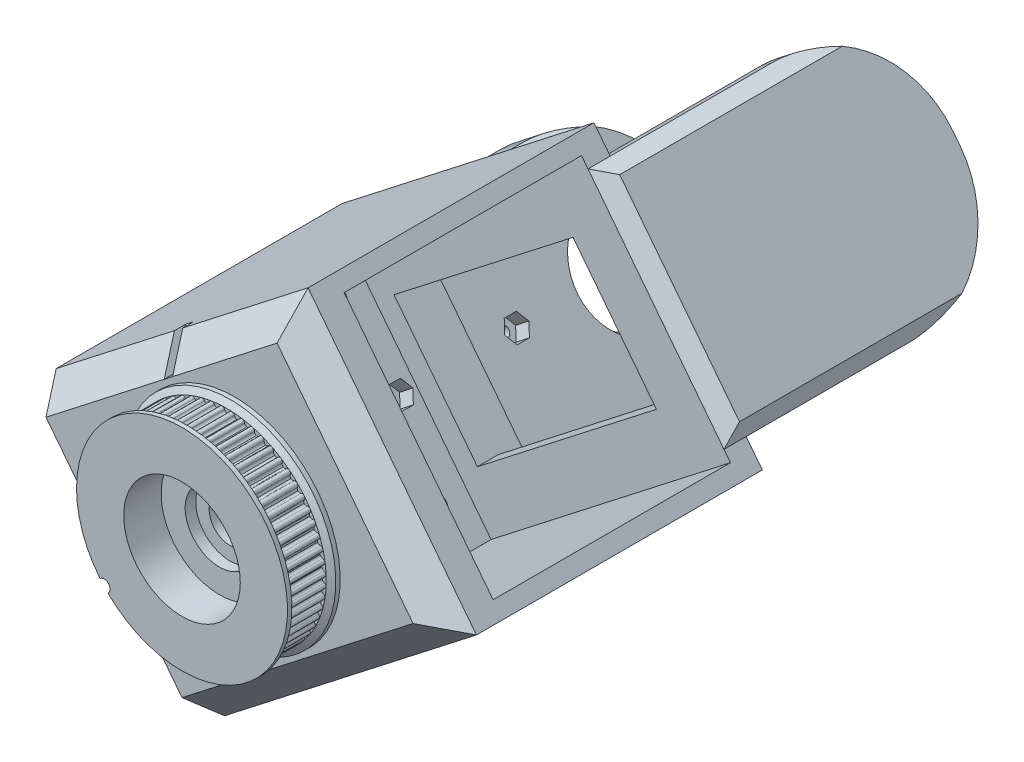
SolidWorks part; units mm, degrees
note: '?' marks a value the reader was unsure of.
other "Camera1"
other "Camera2"
other "Camera3"
ref_plane "Front" through (0, 0, 0) normal (0, 0, 1) x (1, 0, 0)
ref_plane "Top" through (0, 0, 0) normal (0, 1, 0) x (1, 0, 0)
ref_plane "Right" through (0, 0, 0) normal (1, 0, 0) x (0, 0, -1)
sketch "Sketch1" plane through (0, 0, 0) normal (1, 0, 0) x (0, 0, -1)
  line L0 (0, 0) -> (-24.4032, 0) construction
  line L3 (0, 7.1) -> (0, 18.3141)
  line L4 (-1.5, 18.85) -> (-8.5, 18.85)
  line L5 (-10, 20) -> (-10, 7.1)
  line L6 (-10, 7.1) -> (0, 7.1)
  line L7 (0, 18.3141) -> (0, 20)
  line L9 (-0.836, 20) -> (-1.5, 18.85)
  line L10 (-10, 13.3586) -> (0, 13.3586) construction
  line L11 (-5, 18.85) -> (-5, 22.0506) construction
  line L12 (-9.164, 20) -> (-8.5, 18.85)
  line L15 (-10, 20) -> (-8.5, 18.85) construction
  line L16 (-1.5, 18.85) -> (0, 18.3141) construction
  line L17 (-10, 20) -> (-9.164, 20)
  line L18 (-0.836, 20) -> (0, 20)
  point P24 (-5, 13.3586)
  dimension "D2" = 10
  dimension "D3" = 7
  dimension "D4" = 37.7
  dimension "D5" = 40
  dimension "D6" = 120
  dimension "D8" = 14.2
revolve "Revolve1" add sketch "Sketch1" angle 360 about L0
ref_plane "Plane2" through (0, 0, 1.5) normal (0, 0, 1) x (1, 0, 0)
ref_plane "Plane3" through (0, 0, 8.5) normal (0, 0, 1) x (1, 0, 0)
sketch "Sketch3" plane through (0, 0, 1.5) normal (0, 0, 1) x (1, 0, 0)
  line L0 (0.4895, 18.4804) -> (0.4858, 18.4697)
  line L1 (-0.4323, 18.471) -> (-0.436, 18.4817)
  line L2 (-1.3914, 18.4344) -> (-1.394, 18.4234)
  line L3 (-2.3607, 18.3247) -> (-2.3654, 18.3349)
  line L4 (-3.3107, 18.188) -> (-3.3122, 18.1768)
  line L5 (-4.2632, 17.9775) -> (-4.269, 17.9872)
  line L6 (-5.1937, 17.7423) -> (-5.194, 17.731)
  line L7 (-6.119, 17.4334) -> (-6.1258, 17.4424)
  line L8 (-7.0199, 17.1022) -> (-7.019, 17.0909)
  line L9 (-7.9078, 16.6983) -> (-7.9155, 16.7066)
  line L10 (-8.7691, 16.2747) -> (-8.767, 16.2636)
  line L11 (-9.6099, 15.7803) -> (-9.6184, 15.7877)
  line L12 (-10.4222, 15.269) -> (-10.419, 15.2581)
  line L13 (-11.2067, 14.6893) -> (-11.216, 14.6958)
  line L14 (-11.9612, 14.0959) -> (-11.9568, 14.0855)
  line L15 (-12.6808, 13.4374) -> (-12.6907, 13.4429)
  line L16 (-13.3691, 12.7684) -> (-13.3637, 12.7585)
  line L17 (-14.0159, 12.0383) -> (-14.0263, 12.0427)
  line L18 (-14.6305, 11.301) -> (-14.6241, 11.2917)
  line L19 (-15.1975, 10.5073) -> (-15.2083, 10.5106)
  line L20 (-15.7316, 9.7098) -> (-15.7243, 9.7012)
  line L21 (-16.2125, 8.8612) -> (-16.2236, 8.8633)
  line L22 (-16.6604, 8.0122) -> (-16.6522, 8.0044)
  line L23 (-17.05, 7.118) -> (-17.0612, 7.1189)
  line L24 (-17.4066, 6.2268) -> (-17.3977, 6.22)
  line L25 (-17.7006, 5.2968) -> (-17.7119, 5.2965)
  line L26 (-17.9621, 4.3732) -> (-17.9525, 4.3673)
  line L27 (-18.1573, 3.4175) -> (-18.1685, 3.4161)
  line L28 (-18.3209, 2.4717) -> (-18.3107, 2.4669)
  line L29 (-18.415, 1.5008) -> (-18.426, 1.4983)
  line L30 (-18.4789, 0.5431) -> (-18.4682, 0.5394)
  line L31 (-18.471, -0.4323) -> (-18.4817, -0.436)
  line L32 (-18.4344, -1.3914) -> (-18.4234, -1.394)
  line L33 (-18.3247, -2.3607) -> (-18.3349, -2.3654)
  line L34 (-18.188, -3.3107) -> (-18.1768, -3.3122)
  line L35 (-17.9775, -4.2632) -> (-17.9872, -4.269)
  line L36 (-17.7423, -5.1937) -> (-17.731, -5.194)
  line L37 (-17.4334, -6.119) -> (-17.4424, -6.1258)
  line L38 (-17.1022, -7.0199) -> (-17.0909, -7.019)
  line L39 (-16.6983, -7.9078) -> (-16.7066, -7.9155)
  line L40 (-16.2747, -8.7691) -> (-16.2636, -8.767)
  line L41 (-15.7803, -9.6099) -> (-15.7877, -9.6184)
  line L42 (-15.269, -10.4222) -> (-15.2581, -10.419)
  line L43 (-14.6893, -11.2067) -> (-14.6958, -11.216)
  line L44 (-14.0959, -11.9612) -> (-14.0855, -11.9568)
  line L45 (-13.4374, -12.6808) -> (-13.4429, -12.6907)
  line L46 (-12.7684, -13.3691) -> (-12.7585, -13.3637)
  line L47 (-12.0383, -14.0159) -> (-12.0427, -14.0263)
  line L48 (-11.301, -14.6305) -> (-11.2917, -14.6241)
  line L49 (-10.5073, -15.1975) -> (-10.5106, -15.2083)
  line L50 (-9.7098, -15.7316) -> (-9.7012, -15.7243)
  line L51 (-8.8612, -16.2125) -> (-8.8633, -16.2236)
  line L52 (-8.0122, -16.6604) -> (-8.0044, -16.6522)
  line L53 (-7.118, -17.05) -> (-7.1189, -17.0612)
  line L54 (-6.2268, -17.4066) -> (-6.22, -17.3977)
  line L55 (-5.2968, -17.7006) -> (-5.2965, -17.7119)
  line L56 (-4.3732, -17.9621) -> (-4.3673, -17.9525)
  line L57 (-3.4175, -18.1573) -> (-3.4161, -18.1685)
  line L58 (-2.4717, -18.3209) -> (-2.4669, -18.3107)
  line L59 (-1.5008, -18.415) -> (-1.4983, -18.426)
  line L60 (-0.5431, -18.4789) -> (-0.5394, -18.4682)
  line L61 (0.4323, -18.471) -> (0.436, -18.4817)
  line L62 (1.3914, -18.4344) -> (1.394, -18.4234)
  line L63 (2.3607, -18.3247) -> (2.3654, -18.3349)
  line L64 (3.3107, -18.188) -> (3.3122, -18.1768)
  line L65 (4.2632, -17.9775) -> (4.269, -17.9872)
  line L66 (5.1937, -17.7423) -> (5.194, -17.731)
  line L67 (6.119, -17.4334) -> (6.1258, -17.4424)
  line L68 (7.0199, -17.1022) -> (7.019, -17.0909)
  line L69 (7.9078, -16.6983) -> (7.9155, -16.7066)
  line L70 (8.7691, -16.2747) -> (8.767, -16.2636)
  line L71 (9.6099, -15.7803) -> (9.6184, -15.7877)
  line L72 (10.4222, -15.269) -> (10.419, -15.2581)
  line L73 (11.2067, -14.6893) -> (11.216, -14.6958)
  line L74 (11.9612, -14.0959) -> (11.9568, -14.0855)
  line L75 (12.6808, -13.4374) -> (12.6907, -13.4429)
  line L76 (13.3691, -12.7684) -> (13.3637, -12.7585)
  line L77 (14.0159, -12.0383) -> (14.0263, -12.0427)
  line L78 (14.6305, -11.301) -> (14.6241, -11.2917)
  line L79 (15.1975, -10.5073) -> (15.2083, -10.5106)
  line L80 (15.7316, -9.7098) -> (15.7243, -9.7012)
  line L81 (16.2125, -8.8612) -> (16.2236, -8.8633)
  line L82 (16.6604, -8.0122) -> (16.6522, -8.0044)
  line L83 (17.05, -7.118) -> (17.0612, -7.1189)
  line L84 (17.4066, -6.2268) -> (17.3977, -6.22)
  line L85 (17.7006, -5.2968) -> (17.7119, -5.2965)
  line L86 (17.9621, -4.3732) -> (17.9525, -4.3673)
  line L87 (18.1573, -3.4175) -> (18.1685, -3.4161)
  line L88 (18.3209, -2.4717) -> (18.3107, -2.4669)
  line L89 (18.415, -1.5008) -> (18.426, -1.4983)
  line L90 (18.4789, -0.5431) -> (18.4682, -0.5394)
  line L91 (18.471, 0.4323) -> (18.4817, 0.436)
  line L92 (18.4344, 1.3914) -> (18.4234, 1.394)
  line L93 (18.3247, 2.3607) -> (18.3349, 2.3654)
  line L94 (18.188, 3.3107) -> (18.1768, 3.3122)
  line L95 (17.9775, 4.2632) -> (17.9872, 4.269)
  line L96 (17.7423, 5.1937) -> (17.731, 5.194)
  line L97 (17.4334, 6.119) -> (17.4424, 6.1258)
  line L98 (17.1022, 7.0199) -> (17.0909, 7.019)
  line L99 (16.6983, 7.9078) -> (16.7066, 7.9155)
  line L100 (16.2747, 8.7691) -> (16.2636, 8.767)
  line L101 (15.7803, 9.6099) -> (15.7877, 9.6184)
  line L102 (15.269, 10.4222) -> (15.2581, 10.419)
  line L103 (14.6893, 11.2067) -> (14.6958, 11.216)
  line L104 (14.0959, 11.9612) -> (14.0855, 11.9568)
  line L105 (13.4374, 12.6808) -> (13.4429, 12.6907)
  line L106 (12.7684, 13.3691) -> (12.7585, 13.3637)
  line L107 (12.0383, 14.0159) -> (12.0427, 14.0263)
  line L108 (11.301, 14.6305) -> (11.2917, 14.6241)
  line L109 (10.5073, 15.1975) -> (10.5106, 15.2083)
  line L110 (9.7098, 15.7316) -> (9.7012, 15.7243)
  line L111 (8.8141, 16.2382) -> (8.8162, 16.2492)
  line L112 (7.9639, 16.6835) -> (7.9561, 16.6753)
  line L113 (7.0685, 17.0705) -> (7.0694, 17.0818)
  line L114 (6.1763, 17.4246) -> (6.1695, 17.4156)
  line L115 (5.2454, 17.7159) -> (5.2452, 17.7272)
  line L116 (4.3211, 17.9748) -> (4.3153, 17.9651)
  line L117 (3.3649, 18.1671) -> (3.3634, 18.1783)
  line L118 (2.4186, 18.328) -> (2.4138, 18.3178)
  line L119 (1.4475, 18.4193) -> (1.4449, 18.4303)
  arc A0 (-0.436, 18.4817) -> (-1.3914, 18.4344) centre (-0.9065, 18.3126) ccw
  arc A1 (-2.3654, 18.3349) -> (-3.3107, 18.188) centre (-2.8157, 18.1175) ccw
  arc A2 (-4.269, 17.9872) -> (-5.1937, 17.7423) centre (-4.6941, 17.7239) ccw
  arc A3 (-6.1258, 17.4424) -> (-7.0199, 17.1022) centre (-6.521, 17.1362) ccw
  arc A4 (-7.9155, 16.7066) -> (-8.7691, 16.2747) centre (-8.2765, 16.3607) ccw
  arc A5 (-9.6184, 15.7877) -> (-10.4222, 15.269) centre (-9.9413, 15.4059) ccw
  arc A6 (-11.216, 14.6958) -> (-11.9612, 14.0959) centre (-11.4972, 14.2824) ccw
  arc A7 (-12.6907, 13.4429) -> (-13.3691, 12.7684) centre (-12.9272, 13.0023) ccw
  arc A8 (-14.0263, 12.0427) -> (-14.6305, 11.301) centre (-14.2155, 11.5798) ccw
  arc A9 (-15.2083, 10.5106) -> (-15.7316, 9.7098) centre (-15.348, 10.0305) ccw
  arc A10 (-16.2236, 8.8633) -> (-16.6604, 8.0122) centre (-16.3124, 8.3712) ccw
  arc A11 (-17.0612, 7.1189) -> (-17.4066, 6.2268) centre (-17.0981, 6.6203) ccw
  arc A12 (-17.7119, 5.2965) -> (-17.9621, 4.3732) centre (-17.6964, 4.7968) ccw
  arc A13 (-18.1685, 3.4161) -> (-18.3209, 2.4717) centre (-18.1009, 2.9207) ccw
  arc A14 (-18.426, 1.4983) -> (-18.4789, 0.5431) centre (-18.307, 1.0127) ccw
  arc A15 (-18.4817, -0.436) -> (-18.4344, -1.3914) centre (-18.3126, -0.9065) ccw
  arc A16 (-18.3349, -2.3654) -> (-18.188, -3.3107) centre (-18.1175, -2.8157) ccw
  arc A17 (-17.9872, -4.269) -> (-17.7423, -5.1937) centre (-17.7239, -4.6941) ccw
  arc A18 (-17.4424, -6.1258) -> (-17.1022, -7.0199) centre (-17.1362, -6.521) ccw
  arc A19 (-16.7066, -7.9155) -> (-16.2747, -8.7691) centre (-16.3607, -8.2765) ccw
  arc A20 (-15.7877, -9.6184) -> (-15.269, -10.4222) centre (-15.4059, -9.9413) ccw
  arc A21 (-14.6958, -11.216) -> (-14.0959, -11.9612) centre (-14.2824, -11.4972) ccw
  arc A22 (-13.4429, -12.6907) -> (-12.7684, -13.3691) centre (-13.0023, -12.9272) ccw
  arc A23 (-12.0427, -14.0263) -> (-11.301, -14.6305) centre (-11.5798, -14.2155) ccw
  arc A24 (-10.5106, -15.2083) -> (-9.7098, -15.7316) centre (-10.0305, -15.348) ccw
  arc A25 (-8.8633, -16.2236) -> (-8.0122, -16.6604) centre (-8.3712, -16.3124) ccw
  arc A26 (-7.1189, -17.0612) -> (-6.2268, -17.4066) centre (-6.6203, -17.0981) ccw
  arc A27 (-5.2965, -17.7119) -> (-4.3732, -17.9621) centre (-4.7968, -17.6964) ccw
  arc A28 (-3.4161, -18.1685) -> (-2.4717, -18.3209) centre (-2.9207, -18.1009) ccw
  arc A29 (-1.4983, -18.426) -> (-0.5431, -18.4789) centre (-1.0127, -18.307) ccw
  arc A30 (0.436, -18.4817) -> (1.3914, -18.4344) centre (0.9065, -18.3126) ccw
  arc A31 (2.3654, -18.3349) -> (3.3107, -18.188) centre (2.8157, -18.1175) ccw
  arc A32 (4.269, -17.9872) -> (5.1937, -17.7423) centre (4.6941, -17.7239) ccw
  arc A33 (6.1258, -17.4424) -> (7.0199, -17.1022) centre (6.521, -17.1362) ccw
  arc A34 (7.9155, -16.7066) -> (8.7691, -16.2747) centre (8.2765, -16.3607) ccw
  arc A35 (9.6184, -15.7877) -> (10.4222, -15.269) centre (9.9413, -15.4059) ccw
  arc A36 (11.216, -14.6958) -> (11.9612, -14.0959) centre (11.4972, -14.2824) ccw
  arc A37 (12.6907, -13.4429) -> (13.3691, -12.7684) centre (12.9272, -13.0023) ccw
  arc A38 (14.0263, -12.0427) -> (14.6305, -11.301) centre (14.2155, -11.5798) ccw
  arc A39 (15.2083, -10.5106) -> (15.7316, -9.7098) centre (15.348, -10.0305) ccw
  arc A40 (16.2236, -8.8633) -> (16.6604, -8.0122) centre (16.3124, -8.3712) ccw
  arc A41 (17.0612, -7.1189) -> (17.4066, -6.2268) centre (17.0981, -6.6203) ccw
  arc A42 (17.7119, -5.2965) -> (17.9621, -4.3732) centre (17.6964, -4.7968) ccw
  arc A43 (18.1685, -3.4161) -> (18.3209, -2.4717) centre (18.1009, -2.9207) ccw
  arc A44 (18.426, -1.4983) -> (18.4789, -0.5431) centre (18.307, -1.0127) ccw
  arc A45 (18.4817, 0.436) -> (18.4344, 1.3914) centre (18.3126, 0.9065) ccw
  arc A46 (18.3349, 2.3654) -> (18.188, 3.3107) centre (18.1175, 2.8157) ccw
  arc A47 (17.9872, 4.269) -> (17.7423, 5.1937) centre (17.7239, 4.6941) ccw
  arc A48 (17.4424, 6.1258) -> (17.1022, 7.0199) centre (17.1362, 6.521) ccw
  arc A49 (16.7066, 7.9155) -> (16.2747, 8.7691) centre (16.3607, 8.2765) ccw
  arc A50 (15.7877, 9.6184) -> (15.269, 10.4222) centre (15.4059, 9.9413) ccw
  arc A51 (14.6958, 11.216) -> (14.0959, 11.9612) centre (14.2824, 11.4972) ccw
  arc A52 (13.4429, 12.6907) -> (12.7684, 13.3691) centre (13.0023, 12.9272) ccw
  arc A53 (12.0427, 14.0263) -> (11.301, 14.6305) centre (11.5798, 14.2155) ccw
  arc A54 (10.5106, 15.2083) -> (9.7098, 15.7316) centre (10.0305, 15.348) ccw
  arc A55 (8.8162, 16.2492) -> (7.9639, 16.6835) centre (8.3239, 16.3366) ccw
  arc A56 (7.0694, 17.0818) -> (6.1763, 17.4246) centre (6.5707, 17.1172) ccw
  arc A57 (5.2452, 17.7272) -> (4.3211, 17.9748) centre (4.7454, 17.7103) ccw
  arc A58 (3.3634, 18.1783) -> (2.4186, 18.328) centre (2.8682, 18.1093) ccw
  arc A59 (1.4449, 18.4303) -> (0.4895, 18.4804) centre (0.9596, 18.3099) ccw
  spline S0 degree 3 poles (0.4858, 18.4697) (0.4077, 18.2495) (0.2403, 18.0862) (0.0262, 18.0851) knots 0 0 0 0 1 1 1 1
  spline S1 degree 3 poles (0.0262, 18.0851) (-0.1878, 18.0868) (-0.3548, 18.2506) (-0.4323, 18.471) knots 0 0 0 0 1 1 1 1
  spline S2 degree 3 poles (-1.394, 18.4234) (-1.4515, 18.1875) (-1.5982, 18.0156) (-1.8382, 17.9913) knots 0 0 0 0 1 1 1 1
  spline S3 degree 3 poles (-1.8382, 17.9913) (-2.0782, 17.9665) (-2.2567, 18.1053) (-2.3607, 18.3247) knots 0 0 0 0 1 1 1 1
  spline S4 degree 3 poles (-3.3122, 18.1768) (-3.3447, 17.9362) (-3.4726, 17.7498) (-3.7088, 17.7006) knots 0 0 0 0 1 1 1 1
  spline S5 degree 3 poles (-3.7088, 17.7006) (-3.9448, 17.6509) (-4.1368, 17.7702) (-4.2632, 17.9775) knots 0 0 0 0 1 1 1 1
  spline S6 degree 3 poles (-5.194, 17.731) (-5.2012, 17.4883) (-5.309, 17.2896) (-5.5387, 17.216) knots 0 0 0 0 1 1 1 1
  spline S7 degree 3 poles (-5.5387, 17.216) (-5.7682, 17.1418) (-5.9717, 17.2404) (-6.119, 17.4334) knots 0 0 0 0 1 1 1 1
  spline S8 degree 3 poles (-7.019, 17.0909) (-7.0007, 16.8488) (-7.0871, 16.6399) (-7.3079, 16.5427) knots 0 0 0 0 1 1 1 1
  spline S9 degree 3 poles (-7.3079, 16.5427) (-7.5284, 16.445) (-7.7411, 16.5218) (-7.9078, 16.6983) knots 0 0 0 0 1 1 1 1
  spline S10 degree 3 poles (-8.767, 16.2636) (-8.7236, 16.0248) (-8.7877, 15.808) (-8.9971, 15.6882) knots 0 0 0 0 1 1 1 1
  spline S11 degree 3 poles (-8.9971, 15.6882) (-9.2062, 15.568) (-9.4256, 15.6221) (-9.6099, 15.7803) knots 0 0 0 0 1 1 1 1
  spline S12 degree 3 poles (-10.419, 15.2581) (-10.3508, 15.0251) (-10.3919, 14.8028) (-10.5876, 14.6618) knots 0 0 0 0 1 1 1 1
  spline S13 degree 3 poles (-10.5876, 14.6618) (-10.783, 14.5204) (-11.007, 14.5513) (-11.2067, 14.6893) knots 0 0 0 0 1 1 1 1
  spline S14 degree 3 poles (-11.9568, 14.0855) (-11.8647, 13.8608) (-11.8823, 13.6355) (-12.0622, 13.4748) knots 0 0 0 0 1 1 1 1
  spline S15 degree 3 poles (-12.0622, 13.4748) (-12.2418, 13.3137) (-12.4677, 13.321) (-12.6808, 13.4374) knots 0 0 0 0 1 1 1 1
  spline S16 degree 3 poles (-13.3637, 12.7585) (-13.2485, 12.5447) (-13.2425, 12.3187) (-13.4046, 12.1401) knots 0 0 0 0 1 1 1 1
  spline S17 degree 3 poles (-13.4046, 12.1401) (-13.5664, 11.9611) (-13.7918, 11.9448) (-14.0159, 12.0383) knots 0 0 0 0 1 1 1 1
  spline S18 degree 3 poles (-14.6241, 11.2917) (-14.4872, 11.0912) (-14.4576, 10.867) (-14.6002, 10.6725) knots 0 0 0 0 1 1 1 1
  spline S19 degree 3 poles (-14.6002, 10.6725) (-14.7423, 10.4776) (-14.9648, 10.4378) (-15.1975, 10.5073) knots 0 0 0 0 1 1 1 1
  spline S20 degree 3 poles (-15.7243, 9.7012) (-15.5672, 9.5161) (-15.5143, 9.2963) (-15.6358, 9.0879) knots 0 0 0 0 1 1 1 1
  spline S21 degree 3 poles (-15.6358, 9.0879) (-15.7568, 8.8792) (-15.9739, 8.8163) (-16.2125, 8.8612) knots 0 0 0 0 1 1 1 1
  spline S22 degree 3 poles (-16.6522, 8.0044) (-16.4766, 7.8367) (-16.4011, 7.6237) (-16.5001, 7.4037) knots 0 0 0 0 1 1 1 1
  spline S23 degree 3 poles (-16.5001, 7.4037) (-16.5986, 7.1835) (-16.808, 7.0983) (-17.05, 7.118) knots 0 0 0 0 1 1 1 1
  spline S24 degree 3 poles (-17.3977, 6.22) (-17.2055, 6.0715) (-17.1081, 5.8675) (-17.1836, 5.6384) knots 0 0 0 0 1 1 1 1
  spline S25 degree 3 poles (-17.1836, 5.6384) (-17.2585, 5.4091) (-17.4579, 5.3025) (-17.7006, 5.2968) knots 0 0 0 0 1 1 1 1
  spline S26 degree 3 poles (-17.9525, 4.3673) (-17.7459, 4.2398) (-17.6277, 4.0471) (-17.6788, 3.8114) knots 0 0 0 0 1 1 1 1
  spline S27 degree 3 poles (-17.6788, 3.8114) (-17.7294, 3.5755) (-17.9165, 3.4486) (-18.1573, 3.4175) knots 0 0 0 0 1 1 1 1
  spline S28 degree 3 poles (-18.3107, 2.4669) (-18.0919, 2.3616) (-17.9542, 2.1823) (-17.9804, 1.9425) knots 0 0 0 0 1 1 1 1
  spline S29 degree 3 poles (-17.9804, 1.9425) (-18.006, 1.7027) (-18.1788, 1.5569) (-18.415, 1.5008) knots 0 0 0 0 1 1 1 1
  spline S30 degree 3 poles (-18.4682, 0.5394) (-18.2396, 0.4576) (-18.0839, 0.2937) (-18.0849, 0.0524) knots 0 0 0 0 1 1 1 1
  spline S31 degree 3 poles (-18.0849, 0.0524) (-18.0853, -0.1888) (-18.242, -0.3518) (-18.471, -0.4323) knots 0 0 0 0 1 1 1 1
  spline S32 degree 3 poles (-18.4234, -1.394) (-18.1875, -1.4515) (-18.0156, -1.5982) (-17.9913, -1.8382) knots 0 0 0 0 1 1 1 1
  spline S33 degree 3 poles (-17.9913, -1.8382) (-17.9665, -2.0782) (-18.1053, -2.2567) (-18.3247, -2.3607) knots 0 0 0 0 1 1 1 1
  spline S34 degree 3 poles (-18.1768, -3.3122) (-17.9362, -3.3447) (-17.7498, -3.4726) (-17.7006, -3.7088) knots 0 0 0 0 1 1 1 1
  spline S35 degree 3 poles (-17.7006, -3.7088) (-17.6509, -3.9448) (-17.7702, -4.1368) (-17.9775, -4.2632) knots 0 0 0 0 1 1 1 1
  spline S36 degree 3 poles (-17.731, -5.194) (-17.4883, -5.2012) (-17.2896, -5.309) (-17.216, -5.5387) knots 0 0 0 0 1 1 1 1
  spline S37 degree 3 poles (-17.216, -5.5387) (-17.1418, -5.7682) (-17.2404, -5.9717) (-17.4334, -6.119) knots 0 0 0 0 1 1 1 1
  spline S38 degree 3 poles (-17.0909, -7.019) (-16.8488, -7.0007) (-16.6399, -7.0871) (-16.5427, -7.3079) knots 0 0 0 0 1 1 1 1
  spline S39 degree 3 poles (-16.5427, -7.3079) (-16.445, -7.5284) (-16.5218, -7.7411) (-16.6983, -7.9078) knots 0 0 0 0 1 1 1 1
  spline S40 degree 3 poles (-16.2636, -8.767) (-16.0248, -8.7236) (-15.808, -8.7877) (-15.6882, -8.9971) knots 0 0 0 0 1 1 1 1
  spline S41 degree 3 poles (-15.6882, -8.9971) (-15.568, -9.2062) (-15.6221, -9.4256) (-15.7803, -9.6099) knots 0 0 0 0 1 1 1 1
  spline S42 degree 3 poles (-15.2581, -10.419) (-15.0251, -10.3508) (-14.8028, -10.3919) (-14.6618, -10.5876) knots 0 0 0 0 1 1 1 1
  spline S43 degree 3 poles (-14.6618, -10.5876) (-14.5204, -10.783) (-14.5513, -11.007) (-14.6893, -11.2067) knots 0 0 0 0 1 1 1 1
  spline S44 degree 3 poles (-14.0855, -11.9568) (-13.8608, -11.8647) (-13.6355, -11.8823) (-13.4748, -12.0622) knots 0 0 0 0 1 1 1 1
  spline S45 degree 3 poles (-13.4748, -12.0622) (-13.3137, -12.2418) (-13.321, -12.4677) (-13.4374, -12.6808) knots 0 0 0 0 1 1 1 1
  spline S46 degree 3 poles (-12.7585, -13.3637) (-12.5447, -13.2485) (-12.3187, -13.2425) (-12.1401, -13.4046) knots 0 0 0 0 1 1 1 1
  spline S47 degree 3 poles (-12.1401, -13.4046) (-11.9611, -13.5664) (-11.9448, -13.7918) (-12.0383, -14.0159) knots 0 0 0 0 1 1 1 1
  spline S48 degree 3 poles (-11.2917, -14.6241) (-11.0912, -14.4872) (-10.867, -14.4576) (-10.6725, -14.6002) knots 0 0 0 0 1 1 1 1
  spline S49 degree 3 poles (-10.6725, -14.6002) (-10.4776, -14.7423) (-10.4378, -14.9648) (-10.5073, -15.1975) knots 0 0 0 0 1 1 1 1
  spline S50 degree 3 poles (-9.7012, -15.7243) (-9.5161, -15.5672) (-9.2963, -15.5143) (-9.0879, -15.6358) knots 0 0 0 0 1 1 1 1
  spline S51 degree 3 poles (-9.0879, -15.6358) (-8.8792, -15.7568) (-8.8163, -15.9739) (-8.8612, -16.2125) knots 0 0 0 0 1 1 1 1
  spline S52 degree 3 poles (-8.0044, -16.6522) (-7.8367, -16.4766) (-7.6237, -16.4011) (-7.4037, -16.5001) knots 0 0 0 0 1 1 1 1
  spline S53 degree 3 poles (-7.4037, -16.5001) (-7.1835, -16.5986) (-7.0983, -16.808) (-7.118, -17.05) knots 0 0 0 0 1 1 1 1
  spline S54 degree 3 poles (-6.22, -17.3977) (-6.0715, -17.2055) (-5.8675, -17.1081) (-5.6384, -17.1836) knots 0 0 0 0 1 1 1 1
  spline S55 degree 3 poles (-5.6384, -17.1836) (-5.4091, -17.2585) (-5.3025, -17.4579) (-5.2968, -17.7006) knots 0 0 0 0 1 1 1 1
  spline S56 degree 3 poles (-4.3673, -17.9525) (-4.2398, -17.7459) (-4.0471, -17.6277) (-3.8114, -17.6788) knots 0 0 0 0 1 1 1 1
  spline S57 degree 3 poles (-3.8114, -17.6788) (-3.5755, -17.7294) (-3.4486, -17.9165) (-3.4175, -18.1573) knots 0 0 0 0 1 1 1 1
  spline S58 degree 3 poles (-2.4669, -18.3107) (-2.3616, -18.0919) (-2.1823, -17.9542) (-1.9425, -17.9804) knots 0 0 0 0 1 1 1 1
  spline S59 degree 3 poles (-1.9425, -17.9804) (-1.7027, -18.006) (-1.5569, -18.1788) (-1.5008, -18.415) knots 0 0 0 0 1 1 1 1
  spline S60 degree 3 poles (-0.5394, -18.4682) (-0.4576, -18.2396) (-0.2937, -18.0839) (-0.0524, -18.0849) knots 0 0 0 0 1 1 1 1
  spline S61 degree 3 poles (-0.0524, -18.0849) (0.1888, -18.0853) (0.3518, -18.242) (0.4323, -18.471) knots 0 0 0 0 1 1 1 1
  spline S62 degree 3 poles (1.394, -18.4234) (1.4515, -18.1875) (1.5982, -18.0156) (1.8382, -17.9913) knots 0 0 0 0 1 1 1 1
  spline S63 degree 3 poles (1.8382, -17.9913) (2.0782, -17.9665) (2.2567, -18.1053) (2.3607, -18.3247) knots 0 0 0 0 1 1 1 1
  spline S64 degree 3 poles (3.3122, -18.1768) (3.3447, -17.9362) (3.4726, -17.7498) (3.7088, -17.7006) knots 0 0 0 0 1 1 1 1
  spline S65 degree 3 poles (3.7088, -17.7006) (3.9448, -17.6509) (4.1368, -17.7702) (4.2632, -17.9775) knots 0 0 0 0 1 1 1 1
  spline S66 degree 3 poles (5.194, -17.731) (5.2012, -17.4883) (5.309, -17.2896) (5.5387, -17.216) knots 0 0 0 0 1 1 1 1
  spline S67 degree 3 poles (5.5387, -17.216) (5.7682, -17.1418) (5.9717, -17.2404) (6.119, -17.4334) knots 0 0 0 0 1 1 1 1
  spline S68 degree 3 poles (7.019, -17.0909) (7.0007, -16.8488) (7.0871, -16.6399) (7.3079, -16.5427) knots 0 0 0 0 1 1 1 1
  spline S69 degree 3 poles (7.3079, -16.5427) (7.5284, -16.445) (7.7411, -16.5218) (7.9078, -16.6983) knots 0 0 0 0 1 1 1 1
  spline S70 degree 3 poles (8.767, -16.2636) (8.7236, -16.0248) (8.7877, -15.808) (8.9971, -15.6882) knots 0 0 0 0 1 1 1 1
  spline S71 degree 3 poles (8.9971, -15.6882) (9.2062, -15.568) (9.4256, -15.6221) (9.6099, -15.7803) knots 0 0 0 0 1 1 1 1
  spline S72 degree 3 poles (10.419, -15.2581) (10.3508, -15.0251) (10.3919, -14.8028) (10.5876, -14.6618) knots 0 0 0 0 1 1 1 1
  spline S73 degree 3 poles (10.5876, -14.6618) (10.783, -14.5204) (11.007, -14.5513) (11.2067, -14.6893) knots 0 0 0 0 1 1 1 1
  spline S74 degree 3 poles (11.9568, -14.0855) (11.8647, -13.8608) (11.8823, -13.6355) (12.0622, -13.4748) knots 0 0 0 0 1 1 1 1
  spline S75 degree 3 poles (12.0622, -13.4748) (12.2418, -13.3137) (12.4677, -13.321) (12.6808, -13.4374) knots 0 0 0 0 1 1 1 1
  spline S76 degree 3 poles (13.3637, -12.7585) (13.2485, -12.5447) (13.2425, -12.3187) (13.4046, -12.1401) knots 0 0 0 0 1 1 1 1
  spline S77 degree 3 poles (13.4046, -12.1401) (13.5664, -11.9611) (13.7918, -11.9448) (14.0159, -12.0383) knots 0 0 0 0 1 1 1 1
  spline S78 degree 3 poles (14.6241, -11.2917) (14.4872, -11.0912) (14.4576, -10.867) (14.6002, -10.6725) knots 0 0 0 0 1 1 1 1
  spline S79 degree 3 poles (14.6002, -10.6725) (14.7423, -10.4776) (14.9648, -10.4378) (15.1975, -10.5073) knots 0 0 0 0 1 1 1 1
  spline S80 degree 3 poles (15.7243, -9.7012) (15.5672, -9.5161) (15.5143, -9.2963) (15.6358, -9.0879) knots 0 0 0 0 1 1 1 1
  spline S81 degree 3 poles (15.6358, -9.0879) (15.7568, -8.8792) (15.9739, -8.8163) (16.2125, -8.8612) knots 0 0 0 0 1 1 1 1
  spline S82 degree 3 poles (16.6522, -8.0044) (16.4766, -7.8367) (16.4011, -7.6237) (16.5001, -7.4037) knots 0 0 0 0 1 1 1 1
  spline S83 degree 3 poles (16.5001, -7.4037) (16.5986, -7.1835) (16.808, -7.0983) (17.05, -7.118) knots 0 0 0 0 1 1 1 1
  spline S84 degree 3 poles (17.3977, -6.22) (17.2055, -6.0715) (17.1081, -5.8675) (17.1836, -5.6384) knots 0 0 0 0 1 1 1 1
  spline S85 degree 3 poles (17.1836, -5.6384) (17.2585, -5.4091) (17.4579, -5.3025) (17.7006, -5.2968) knots 0 0 0 0 1 1 1 1
  spline S86 degree 3 poles (17.9525, -4.3673) (17.7459, -4.2398) (17.6277, -4.0471) (17.6788, -3.8114) knots 0 0 0 0 1 1 1 1
  spline S87 degree 3 poles (17.6788, -3.8114) (17.7294, -3.5755) (17.9165, -3.4486) (18.1573, -3.4175) knots 0 0 0 0 1 1 1 1
  spline S88 degree 3 poles (18.3107, -2.4669) (18.0919, -2.3616) (17.9542, -2.1823) (17.9804, -1.9425) knots 0 0 0 0 1 1 1 1
  spline S89 degree 3 poles (17.9804, -1.9425) (18.006, -1.7027) (18.1788, -1.5569) (18.415, -1.5008) knots 0 0 0 0 1 1 1 1
  spline S90 degree 3 poles (18.4682, -0.5394) (18.2396, -0.4576) (18.0839, -0.2937) (18.0849, -0.0524) knots 0 0 0 0 1 1 1 1
  spline S91 degree 3 poles (18.0849, -0.0524) (18.0853, 0.1888) (18.242, 0.3518) (18.471, 0.4323) knots 0 0 0 0 1 1 1 1
  spline S92 degree 3 poles (18.4234, 1.394) (18.1875, 1.4515) (18.0156, 1.5982) (17.9913, 1.8382) knots 0 0 0 0 1 1 1 1
  spline S93 degree 3 poles (17.9913, 1.8382) (17.9665, 2.0782) (18.1053, 2.2567) (18.3247, 2.3607) knots 0 0 0 0 1 1 1 1
  spline S94 degree 3 poles (18.1768, 3.3122) (17.9362, 3.3447) (17.7498, 3.4726) (17.7006, 3.7088) knots 0 0 0 0 1 1 1 1
  spline S95 degree 3 poles (17.7006, 3.7088) (17.6509, 3.9448) (17.7702, 4.1368) (17.9775, 4.2632) knots 0 0 0 0 1 1 1 1
  spline S96 degree 3 poles (17.731, 5.194) (17.4883, 5.2012) (17.2896, 5.309) (17.216, 5.5387) knots 0 0 0 0 1 1 1 1
  spline S97 degree 3 poles (17.216, 5.5387) (17.1418, 5.7682) (17.2404, 5.9717) (17.4334, 6.119) knots 0 0 0 0 1 1 1 1
  spline S98 degree 3 poles (17.0909, 7.019) (16.8488, 7.0007) (16.6399, 7.0871) (16.5427, 7.3079) knots 0 0 0 0 1 1 1 1
  spline S99 degree 3 poles (16.5427, 7.3079) (16.445, 7.5284) (16.5218, 7.7411) (16.6983, 7.9078) knots 0 0 0 0 1 1 1 1
  spline S100 degree 3 poles (16.2636, 8.767) (16.0248, 8.7236) (15.808, 8.7877) (15.6882, 8.9971) knots 0 0 0 0 1 1 1 1
  spline S101 degree 3 poles (15.6882, 8.9971) (15.568, 9.2062) (15.6221, 9.4256) (15.7803, 9.6099) knots 0 0 0 0 1 1 1 1
  spline S102 degree 3 poles (15.2581, 10.419) (15.0251, 10.3508) (14.8028, 10.3919) (14.6618, 10.5876) knots 0 0 0 0 1 1 1 1
  spline S103 degree 3 poles (14.6618, 10.5876) (14.5204, 10.783) (14.5513, 11.007) (14.6893, 11.2067) knots 0 0 0 0 1 1 1 1
  spline S104 degree 3 poles (14.0855, 11.9568) (13.8608, 11.8647) (13.6355, 11.8823) (13.4748, 12.0622) knots 0 0 0 0 1 1 1 1
  spline S105 degree 3 poles (13.4748, 12.0622) (13.3137, 12.2418) (13.321, 12.4677) (13.4374, 12.6808) knots 0 0 0 0 1 1 1 1
  spline S106 degree 3 poles (12.7585, 13.3637) (12.5447, 13.2485) (12.3187, 13.2425) (12.1401, 13.4046) knots 0 0 0 0 1 1 1 1
  spline S107 degree 3 poles (12.1401, 13.4046) (11.9611, 13.5664) (11.9448, 13.7918) (12.0383, 14.0159) knots 0 0 0 0 1 1 1 1
  spline S108 degree 3 poles (11.2917, 14.6241) (11.0912, 14.4872) (10.867, 14.4576) (10.6725, 14.6002) knots 0 0 0 0 1 1 1 1
  spline S109 degree 3 poles (10.6725, 14.6002) (10.4776, 14.7423) (10.4378, 14.9648) (10.5073, 15.1975) knots 0 0 0 0 1 1 1 1
  spline S110 degree 3 poles (9.7012, 15.7243) (9.5161, 15.5672) (9.5993, 15.3388) (9.0425, 15.6621) knots 0 0 0 0 1 1 1 1
  spline S111 degree 3 poles (9.0425, 15.6621) (8.8334, 15.7824) (8.77, 15.9994) (8.8141, 16.2382) knots 0 0 0 0 1 1 1 1
  spline S112 degree 3 poles (7.9561, 16.6753) (7.7889, 16.4993) (7.5761, 16.4231) (7.3558, 16.5215) knots 0 0 0 0 1 1 1 1
  spline S113 degree 3 poles (7.3558, 16.5215) (7.1353, 16.6193) (7.0495, 16.8285) (7.0685, 17.0705) knots 0 0 0 0 1 1 1 1
  spline S114 degree 3 poles (6.1695, 17.4156) (6.0216, 17.2231) (5.8179, 17.125) (5.5886, 17.1999) knots 0 0 0 0 1 1 1 1
  spline S115 degree 3 poles (5.5886, 17.1999) (5.3591, 17.2741) (5.2519, 17.4732) (5.2454, 17.7159) knots 0 0 0 0 1 1 1 1
  spline S116 degree 3 poles (4.3153, 17.9651) (4.1883, 17.7581) (3.996, 17.6394) (3.7601, 17.6898) knots 0 0 0 0 1 1 1 1
  spline S117 degree 3 poles (3.7601, 17.6898) (3.5241, 17.7397) (3.3967, 17.9264) (3.3649, 18.1671) knots 0 0 0 0 1 1 1 1
  spline S118 degree 3 poles (2.4138, 18.3178) (2.3091, 18.0986) (2.1303, 17.9604) (1.8904, 17.9859) knots 0 0 0 0 1 1 1 1
  spline S119 degree 3 poles (1.8904, 17.9859) (1.6505, 18.0109) (1.5042, 18.1832) (1.4475, 18.4193) knots 0 0 0 0 1 1 1 1
extrude "Cut-Extrude1" cut sketch "Sketch3" along normal up to surface (7 mm away) flip side to cut up to plane "Plane3"
sketch "Sketch4" plane through (0, 0, 10) normal (0, 0, 1) x (1, 0, 0)
  circle A0 centre (0, 15) radius 1.75
  circle A1 centre (15, 0) radius 1.75
  circle A2 centre (0, -15) radius 1.75
  circle A3 centre (-15, 0) radius 1.75
  point P12 (0, 0)
  dimension "D1" = 3.5
  dimension "D2" = 15
  dimension "D3" = 4
sketch "草图1" plane through (0, 0, 0) normal (0, 0, -1) x (-1, 0, 0)
  line L0 (-8.4198, 33.1528) -> (34.2053, 0)
  line L1 (34.2053, 0) -> (8.4198, -33.1528)
  line L2 (8.4198, -33.1528) -> (-34.2053, 0)
  line L3 (-34.2053, 0) -> (-8.4198, 33.1528)
  line L4 (-34.2053, 0) -> (34.2053, 0) construction
  point P2 (0, 0)
  dimension "D1" = 42
  dimension "D2" = 54
extrude "凸台-拉伸1" add sketch "草图1" along normal blind 10
sketch "草图2" plane through (0, 0, -10) normal (0, 0, -1) x (-1, 0, 0)
  line L0 (-8.4198, 33.1528) -> (33.4159, 0.6139)
  line L1 (34.2053, 0) -> (-8.4198, 33.1528) construction
  line L2 (33.4159, 0.6139) -> (7.6304, -32.5389)
  line L3 (-34.2053, 0) -> (8.4198, -33.1528) construction
  line L4 (7.6304, -32.5389) -> (-34.2053, 0)
  line L5 (-34.2053, 0) -> (-8.4198, 33.1528)
  line L6 (33.4159, 0.6139) -> (34.2053, 0)
  line L7 (34.2053, 0) -> (8.4198, -33.1528)
  line L8 (8.4198, -33.1528) -> (7.6304, -32.5389)
  line L9 (33.4159, 0.6139) -> (7.6304, -32.5389)
  line M6 (-34.2053, 0) -> (8.4198, -33.1528)
  line M7 (8.4198, -33.1528) -> (34.2053, 0)
  line M8 (34.2053, 0) -> (-8.4198, 33.1528)
  dimension "49" = 53
extrude "凸台-拉伸2" add sketch "草图2" along normal blind 45 contours L2 M8 M6 M7
sketch "草图4" plane through (0, 0, -55) normal (0, 0, -1) x (-1, 0, 0)
  line L4 (39.7307, -4.2976) -> (-13.9452, 37.4504)
  line L5 (-13.9452, 37.4504) -> (-39.7307, 4.2976)
  line L6 (-39.7307, 4.2976) -> (13.9452, -37.4504)
  line L7 (13.9452, -37.4504) -> (39.7307, -4.2976)
  line L8 (7.6304, -32.5389) -> (8.4198, -33.1528) construction
  line L9 (34.2053, 0) -> (33.4159, 0.6139) construction
  line L10 (-39.7307, 4.2976) -> (39.7307, -4.2976) construction
  line L11 (34.2053, 0) -> (-34.2053, 0) construction
  point P21 (0, 0)
  point P22 (0, 0)
  dimension "D1" = 68
extrude "凸台-拉伸3" add sketch "草图4" along normal blind 8
sketch "草图27" plane through (-21.3125, -16.5764, 0) normal (-0.7894, -0.6139, 0) x (0, 0, 1)
  line L0 (0, 21) -> (0, -21)
  line L1 (0, -21) -> (-55, -21)
  line L2 (-55, -21) -> (-55, 21)
  line L3 (-55, 21) -> (0, 21)
extrude "凸台-拉伸10" add sketch "草图27" along normal blind 7
sketch "草图8" plane through (0, 0, -63) normal (0, 0, -1) x (-1, 0, 0)
  line L0 (-13.9452, 37.4504) -> (-7.6304, 32.5389)
  line L1 (39.7307, -4.2976) -> (-13.9452, 37.4504) construction
  line L2 (-7.6304, 32.5389) -> (-33.4159, -0.6139)
  line L3 (-39.7307, 4.2976) -> (13.9452, -37.4504) construction
  line L4 (-33.4159, -0.6139) -> (-39.7307, 4.2976)
  line L5 (-39.7307, 4.2976) -> (-13.9452, 37.4504)
  line L6 (39.7307, -4.2976) -> (33.4159, 0.6139)
  line L7 (33.4159, 0.6139) -> (7.6304, -32.5389)
  line L8 (7.6304, -32.5389) -> (13.9452, -37.4504)
  line L9 (13.9452, -37.4504) -> (39.7307, -4.2976)
  line M9 (13.9452, -37.4504) -> (39.7307, -4.2976)
  line M10 (39.7307, -4.2976) -> (-13.9452, 37.4504)
  line M12 (-39.7307, 4.2976) -> (13.9452, -37.4504)
  dimension "D1" = 52
extrude "凸台-拉伸6" add sketch "草图8" along normal blind 47 contours L7 M10 M12 M9 | L5 L0 L2 L4
sketch "草图3" plane through (-20.5232, -15.9625, 0) normal (0.7894, 0.6139, 0) x (0, 0, -1)
  line L1 (17, -15.5) -> (46, 15.5) construction
  line L2 (46, -15.5) -> (46, 15.5) construction
  line L3 (46, 15.5) -> (17, 15.5) construction
  line L4 (17, 15.5) -> (17, -15.5) construction
  line L5 (17, -15.5) -> (46, -15.5) construction
  line L6 (42.5, -15.5) -> (49.5, -15.5) construction
  line L9 (42.5, -13.9) -> (49.5, -13.9)
  line L10 (42.5, -17.1) -> (49.5, -17.1)
  line L11 (14, -15.5) -> (20, -15.5) construction
  line L12 (14, -13.9) -> (20, -13.9)
  line L13 (14, -17.1) -> (20, -17.1)
  line L14 (14, 15.5) -> (20, 15.5) construction
  line L15 (14, 17.1) -> (20, 17.1)
  line L16 (14, 13.9) -> (20, 13.9)
  line L17 (42.5, 15.5) -> (49.5, 15.5) construction
  line L18 (42.5, 17.1) -> (49.5, 17.1)
  line L19 (42.5, 13.9) -> (49.5, 13.9)
  line L20 (34, 0) -> (29, 0) construction
  line L21 (34, -11.1) -> (29, -11.1)
  line L22 (34, 11.1) -> (29, 11.1)
  line L24 (10, 21) -> (10, -21) construction
  arc A7 (42.5, -13.9) -> (42.5, -17.1) centre (42.5, -15.5) ccw
  arc A8 (49.5, -17.1) -> (49.5, -13.9) centre (49.5, -15.5) ccw
  arc A9 (14, -13.9) -> (14, -17.1) centre (14, -15.5) ccw
  arc A10 (20, -17.1) -> (20, -13.9) centre (20, -15.5) ccw
  arc A11 (14, 17.1) -> (14, 13.9) centre (14, 15.5) ccw
  arc A12 (20, 13.9) -> (20, 17.1) centre (20, 15.5) ccw
  arc A13 (42.5, 17.1) -> (42.5, 13.9) centre (42.5, 15.5) ccw
  arc A14 (49.5, 13.9) -> (49.5, 17.1) centre (49.5, 15.5) ccw
  arc A15 (34, -11.1) -> (34, 11.1) centre (34, 0) ccw
  arc A16 (29, 11.1) -> (29, -11.1) centre (29, 0) ccw
  point P1 (31.5, 0)
  point P13 (46, -15.5)
  point P18 (31.5, 0)
  point P21 (17, -15.5)
  point P28 (17, 15.5)
  point P35 (46, 15.5)
  dimension "D1" = 22.2
  dimension "D3" = 7
  dimension "D4" = 5
  dimension "D2" = 31
  dimension "D5" = 3.2
  dimension "D6" = 29
  dimension "D7" = 7
  dimension "D8" = 6
extrude "切除-拉伸1" cut sketch "草图3" against normal blind 42
sketch "草图9" plane through (-20.5232, -15.9625, 0) normal (0.7894, 0.6139, 0) x (0, 0, -1)
  line L0 (96, 21) -> (96, -21) construction
  line L1 (110, 21) -> (63, 21) construction
  line L2 (110, -21) -> (63, -21) construction
  circle A0 centre (96, 0) radius 9
  dimension "D1" = 18
  dimension "D2" = 33
extrude "切除-拉伸2" cut sketch "草图9" against normal blind 10
sketch "草图10" plane through (-20.5232, -15.9625, 0) normal (0.7894, 0.6139, 0) x (0, 0, -1)
  circle A0 centre (96, 0) radius 10.55
  dimension "D1" = 21.1
extrude "切除-拉伸3" cut sketch "草图10" against normal blind 4
sketch "草图11" plane through (-26.838, -20.874, 0) normal (-0.7894, -0.6139, 0) x (0, 0, 1)
  circle A0 centre (-96, 0) radius 10.55
  dimension "D1" = 21.1
extrude "切除-拉伸4" cut sketch "草图11" against normal blind 3.5
sketch "草图12" plane through (20.5232, 15.9625, 0) normal (-0.7894, -0.6139, 0) x (0, 0, 1)
  circle A0 centre (-96, 0) radius 10.55
  circle A1 centre (-96, 0) radius 10.55 construction
  dimension "D1" = 21.1
extrude "切除-拉伸5" cut sketch "草图12" against normal blind 4
sketch "草图13" plane through (23.6806, 18.4182, 0) normal (-0.7894, -0.6139, 0) x (0, 0, 1)
  circle A0 centre (-96, 0) radius 8.9
  dimension "D1" = 17.8
extrude "切除-拉伸6" cut sketch "草图13" against normal blind 3
sketch "草图14" plane through (0, 0, 10) normal (0, 0, 1) x (1, 0, 0)
  circle A0 centre (0, 0) radius 11.05
  dimension "D1" = 22.1
extrude "切除-拉伸7" cut sketch "草图14" against normal blind 7.1
sketch "草图15" plane through (0, 0, 2.9) normal (0, 0, 1) x (1, 0, 0)
  circle A0 centre (0, 0) radius 3.95
  dimension "D1" = 7.9
chamfer "倒角1" distance 2.5 angle 45 9 edges at (7.6304, 32.5389, -86.5) (33.4159, -0.6139, -86.5) (12.8928, -16.5764, -63) (-7.6304, -32.5389, -86.5) (-33.4159, 0.6139, -86.5) (-12.8928, 16.5764, -63) (39.7307, 4.2976, -82.5) (26.838, 20.874, -55) (13.9452, 37.4504, -82.5)
fillet "圆角1" radius 20 10 edges at (-37.56, -2.6092, -110) (-11.7745, -35.762, -110) (36.5733, 1.8418, -110) (-33.6352, -1.1402, -110) (-9.3845, -32.3196, -110) (10.7878, 34.9946, -110) (9.3845, 32.3196, -110) (13.726, 35.6963, -110) (37.9766, 4.5168, -110) (33.6352, 1.1402, -110)
sketch "草图18" plane through (0, 0, -10) normal (0, 0, -1) x (-1, 0, 0)
  line L0 (3.7239, -6.45) -> (7.4478, 0)
  line L1 (7.4478, 0) -> (3.7239, 6.45)
  line L2 (3.7239, 6.45) -> (-3.7239, 6.45)
  line L3 (-3.7239, 6.45) -> (-7.4478, 0)
  line L4 (-7.4478, 0) -> (-3.7239, -6.45)
  line L5 (-3.7239, -6.45) -> (3.7239, -6.45)
  circle A0 centre (0, 0) radius 6.45 construction
  circle A2 centre (0, 0) radius 7.1 construction
  dimension "D1" = 12.9
extrude "切除-拉伸10" cut sketch "草图18" against normal blind 8.2
sketch "草图21" plane through (0, 0, 0) normal (0, 0, 1) x (1, 0, 0)
  circle A0 centre (0, 0) radius 7.1
extrude "凸台-拉伸9" add sketch "草图21" along normal up to surface (2.9 mm away) up to face at (7.1, 0, 2.9)
sketch "草图20" plane through (0, 0, 2.9) normal (0, 0, 1) x (1, 0, 0)
  circle A0 centre (0, 0) radius 6.5
  dimension "D1" = 13
extrude "切除-拉伸11" cut sketch "草图20" against normal blind 2
sketch "草图22" plane through (-26.838, -20.874, 0) normal (-0.7894, -0.6139, 0) x (0, 0, 1)
  line L0 (-51.1, -15.5) -> (-40.9, -15.5)
  line L3 (-21.6, -15.5) -> (-12.4, -15.5)
  line L4 (-51.1, 15.5) -> (-40.9, 15.5)
  line L6 (-21.6, 15.5) -> (-12.4, 15.5)
  line L8 (-13, -15.5) -> (-21, -15.5) construction
  line L9 (-13, -18.25) -> (-21, -18.25)
  line L10 (-13, -12.75) -> (-21, -12.75)
  line L11 (-41, -15.5) -> (-51, -15.5) construction
  line L12 (-41, -18.4221) -> (-51, -18.4221)
  line L13 (-41, -12.5779) -> (-51, -12.5779)
  line L14 (-41, 15.5) -> (-51, 15.5) construction
  line L15 (-41, 12.5779) -> (-51, 12.5779)
  line L16 (-41, 18.4221) -> (-51, 18.4221)
  line L17 (-13, 15.5) -> (-21, 15.5) construction
  line L18 (-13, 12.75) -> (-21, 12.75)
  line L19 (-13, 18.25) -> (-21, 18.25)
  arc A4 (-20, 17.1) -> (-20, 13.9) centre (-20, 15.5) ccw construction
  arc A5 (-14, 13.9) -> (-14, 17.1) centre (-14, 15.5) ccw construction
  arc A6 (-20, -13.9) -> (-20, -17.1) centre (-20, -15.5) ccw construction
  arc A7 (-14, -17.1) -> (-14, -13.9) centre (-14, -15.5) ccw construction
  arc A10 (-49.5, 17.1) -> (-49.5, 13.9) centre (-49.5, 15.5) ccw construction
  arc A11 (-42.5, 13.9) -> (-42.5, 17.1) centre (-42.5, 15.5) ccw construction
  arc A12 (-13, -18.25) -> (-13, -12.75) centre (-13, -15.5) ccw
  arc A13 (-21, -12.75) -> (-21, -18.25) centre (-21, -15.5) ccw
  arc A14 (-41, -18.4221) -> (-41, -12.5779) centre (-41, -15.5) ccw
  arc A15 (-51, -12.5779) -> (-51, -18.4221) centre (-51, -15.5) ccw
  arc A16 (-41, 12.5779) -> (-41, 18.4221) centre (-41, 15.5) ccw
  arc A17 (-51, 18.4221) -> (-51, 12.5779) centre (-51, 15.5) ccw
  arc A18 (-13, 12.75) -> (-13, 18.25) centre (-13, 15.5) ccw
  arc A19 (-21, 18.25) -> (-21, 12.75) centre (-21, 15.5) ccw
  arc A20 (-49.5, -13.9) -> (-49.5, -17.1) centre (-49.5, -15.5) ccw construction
  arc A21 (-42.5, -17.1) -> (-42.5, -13.9) centre (-42.5, -15.5) ccw construction
  point P19 (-17, 15.5)
  point P28 (-17, -15.5)
  point P34 (-17, -15.5)
  point P39 (-46, 15.5)
  point P43 (-46, -15.5)
  point P50 (-46, 15.5)
  point P57 (-17, 15.5)
  point P64 (-46, -15.5)
  dimension "D4" = 8
  dimension "D1" = 5.5
  dimension "D2" = 8
  dimension "D3" = 10
extrude "切除-拉伸13" cut sketch "草图22" against normal blind 2
sketch "草图24" plane through (0, 0, 10) normal (0, 0, 1) x (1, 0, 0)
  circle A1 centre (-12.4451, -14.5664) radius 1.1
  dimension "D1" = 2.2
ref_axis "基准轴1" through (0, 0, -93.4934) along (0, 0, 1)?
sketch "草图28" plane through (0, 0, -63) normal (0, 0, -1) x (-1, 0, 0)
  line L0 (-11.3579, -14.603) -> (-3.8472, -3.8472)
  line L1 (-31.8811, 1.3594) -> (9.1653, -30.5655) construction
extrude "切除-拉伸18" cut sketch "草图15" against normal blind 10
sketch "草图34" plane through (0, 0, -63) normal (0, 0, -1) x (-1, 0, 0)
  line L0 (-5.6132, 27.8027) -> (28.329, 1.4033)
  line L1 (31.8811, -1.3594) -> (-9.1653, 30.5655) construction
  line L2 (28.329, 1.4033) -> (5.6132, -27.8027)
  line L3 (-31.8811, 1.3594) -> (9.1653, -30.5655) construction
  line L4 (5.6132, -27.8027) -> (-28.329, -1.4033)
  line L5 (-28.329, -1.4033) -> (-5.6132, 27.8027)
  point P4 (11.3579, 14.603)
  point P9 (11.3579, 14.603)
  dimension "D1" = 43
extrude "切除-拉伸20" cut sketch "草图34" against normal blind 4
fillet "圆角3" radius 5 2 edges at (-11.3579, 14.603, -63) (11.3579, -14.603, -63)
sketch "草图35" plane through (-26.838, -20.874, 0) normal (-0.7894, -0.6139, 0) x (0, 0, 1)
  circle A0 centre (-52, 0) radius 1
  circle A1 centre (-74, 0) radius 1
extrude "切除-拉伸21" cut sketch "草图35" against normal blind 10
sketch "草图36" plane through (-20.5232, -15.9625, 0) normal (0.7894, 0.6139, 0) x (0, 0, -1)
  line L12 (53.1547, -2) -> (54.3094, 0)
  line L13 (54.3094, 0) -> (53.1547, 2)
  line L14 (53.1547, 2) -> (50.8453, 2)
  line L15 (50.8453, 2) -> (49.6922, 0.0028)
  line L16 (49.6922, 0.0028) -> (50.8421, -2)
  line L17 (50.8421, -2) -> (53.1547, -2)
  line L18 (75.1547, -2) -> (76.3094, 0)
  line L19 (76.3094, 0) -> (75.1547, 2)
  line L20 (75.1547, 2) -> (72.8453, 2)
  line L21 (72.8453, 2) -> (71.6922, 0.0028)
  line L22 (71.6922, 0.0028) -> (72.8421, -2)
  line L23 (72.8421, -2) -> (75.1547, -2)
  circle A0 centre (52, 0) radius 2 construction
  circle A2 centre (74, 0) radius 2 construction
  circle A3 centre (52, 0) radius 1 construction
  circle A4 centre (74, 0) radius 1 construction
  dimension "D1" = 4
  dimension "D2" = 4
extrude "切除-拉伸22" cut sketch "草图36" against normal blind 3.2
sketch "草图38" plane through (0, 0, 10) normal (0, 0, 1) x (1, 0, 0)
  circle A0 centre (-14.7477, -13.3707) radius 1.1
  circle A2 centre (-14.7477, -13.3707) radius 1 construction
extrude "切除-拉伸24" cut sketch "草图38" against normal blind 1.5
sketch "草图39" plane through (12.8928, -16.5764, 0) normal (0.6139, -0.7894, 0) x (0.7894, 0.6139, 0)
  line L0 (27, 0) -> (-34, 0)
  line L1 (-34, 0) -> (-34, -59.2069)
  line L3 (-34, -59.2069) -> (27, -59.2069)
  line L7 (27, 0) -> (27, -59.2069)
  line L10 (-34, -90) -> (-34, 0) construction
  line L11 (-21.5, -59.2069) -> (21.5, -59.2069) construction
  line L12 (27, 0) -> (-34, 0) construction
extrude "凸台-拉伸12" add sketch "草图39" along normal blind 5
sketch "草图41" plane through (12.8928, -16.5764, 0) normal (-0.6139, 0.7894, 0) x (0.7894, 0.6139, 0)
  line L0 (27, 55) -> (-26, 55)
  line L1 (-26, 55) -> (-26, 10)
  line L2 (27, 10) -> (-26, 10) construction
  line L3 (-26, 10) -> (27, 10)
  line L4 (27, 55) -> (27, 10) construction
  line L5 (27, 10) -> (27, 55)
  line L6 (-26, 55) -> (-26, 10) construction
extrude "切除-拉伸25" cut sketch "草图41" against normal blind 2 contours L5 L0 L1 L3
sketch "草图44" plane through (-12.8928, 16.5764, 0) normal (-0.6139, 0.7894, 0) x (0.7894, 0.6139, 0)
  line L0 (27, 0) -> (27, 59.2069)
  line L1 (27, 59.2069) -> (-34, 59.2069)
  line L3 (-34, 59.2069) -> (-34, 0)
  line L4 (-34, 0) -> (27, 0)
  line L5 (-34, 59.2069) -> (-21.5, 59.2069) construction
  line L6 (-34, 90) -> (-34, 0) construction
  line L7 (-34, 0) -> (27, 0) construction
extrude "凸台-拉伸13" add sketch "草图44" along normal blind 5
sketch "草图45" plane through (-12.8928, 16.5764, 0) normal (0.6139, -0.7894, 0) x (0.7894, 0.6139, 0)
  line L0 (27, -55) -> (-26, -55)
  line L1 (-26, -55) -> (-26, -10)
  line L2 (-26, -10) -> (27, -10)
  line L3 (27, -10) -> (27, -55) construction
  line L4 (27, -10) -> (27, -55)
  line L6 (-26, -55) -> (-26, -10) construction
extrude "切除-拉伸26" cut sketch "草图45" against normal blind 2
sketch "草图49" plane through (21.3125, 16.5764, 0) normal (0.7894, 0.6139, 0) x (0, 0, -1)
  line L0 (59.2069, 21) -> (59.2069, 26)
  line L1 (59.2069, 26) -> (0, 26)
  line L2 (0, 26) -> (0, -26)
  line L3 (0, -26) -> (59.2069, -26)
  line L4 (59.2069, -26) -> (59.2069, -21)
  line L5 (59.2069, -21) -> (55, -21)
  line L6 (55, -21) -> (55, -23)
  line L7 (55, -23) -> (10, -23)
  line L8 (10, -23) -> (10, 23)
  line L9 (10, 23) -> (55, 23)
  line L10 (55, 23) -> (55, 21)
  line L11 (55, 23) -> (55, 21) construction
  line L12 (55, 23) -> (55, -23) construction
  line L13 (55, 21) -> (59.2069, 21)
extrude "凸台-拉伸14" add sketch "草图49" along normal blind 4.5
chamfer "倒角3" distance 5 angle 45 6 edges at (24.8646, 19.3391, 0) (-26.838, -20.874, 0) (14.9758, -21.2906, 0) (-16.9491, 19.7557, 0) (-10.8755, -41.3971, -29.6034) (-42.8004, -0.3508, -29.6034)
sketch "草图52" plane through (0, 0, -59) normal (0, 0, -1) x (-1, 0, 0)
  line L0 (-24.9523, 2.9381) -> (-9.1398, 23.2685)
  line L1 (-5.6132, 27.8027) -> (-28.329, -1.4033) construction
  line L3 (24.8024, -3.1309) -> (8.9898, -23.4613)
  line L4 (-5.6132, 27.8027) -> (-28.329, -1.4033) construction
  line L6 (-24.9523, 2.9381) -> (8.9898, -23.4613)
  line L7 (5.6132, -27.8027) -> (28.329, 1.4033) construction
  line L9 (-9.1398, 23.2685) -> (24.8024, -3.1309)
  line L10 (5.6132, -27.8027) -> (28.329, 1.4033) construction
extrude "切除-拉伸30" cut sketch "草图52" against normal blind 10
ref_plane "基准面2" through (0.3157, 0.2456, 0) normal (-0.7894, -0.6139, 0) x (0, 0, 1)
sketch "草图54" plane through (0.3157, 0.2456, 0) normal (-0.7894, -0.6139, 0) x (0, 0, 1)
  line L3 (-2.1213, 21) -> (-2.1213, 26) construction
  line L4 (-5, 21) -> (0, 21) construction
  line L5 (-2.1213, 26) -> (-7.1213, 26)
  line L7 (-7.1213, 26) -> (-2.1213, 21)
  line L8 (-5, 26) -> (0, 21) construction
  line L9 (-59.2069, 26) -> (-5, 26) construction
  line L10 (-2.1213, 26) -> (0, 25.9505)
  line L11 (0, 25.9505) -> (0, 21)
  line L12 (0, 21) -> (-2.1213, 21)
  dimension "D1" = 1.5
extrude "切除-拉伸32" cut sketch "草图54" against normal mid plane 2
sketch "草图55" plane through (0, 0, -110) normal (0, 0, -1) x (-1, 0, 0)
  line L0 (-21.1371, 15.1731) -> (-19.9092, 16.7518)
  line L1 (-19.9092, 16.7518) -> (-23.856, 19.8215)
  line L2 (-23.856, 19.8215) -> (-25.0839, 18.2428)
  line L3 (-25.0839, 18.2428) -> (-21.1371, 15.1731)
  line L4 (-19.9092, 16.7518) -> (-26.224, 21.6633) construction
  line L5 (-19.9092, 16.7518) -> (-21.1371, 15.1731) construction
  point P6 (-20.5232, 15.9625)
  point P10 (-20.5232, 15.9625)
  dimension "D1" = 2
  dimension "D2" = 5
extrude "切除-拉伸33" cut sketch "草图55" against normal blind 2
